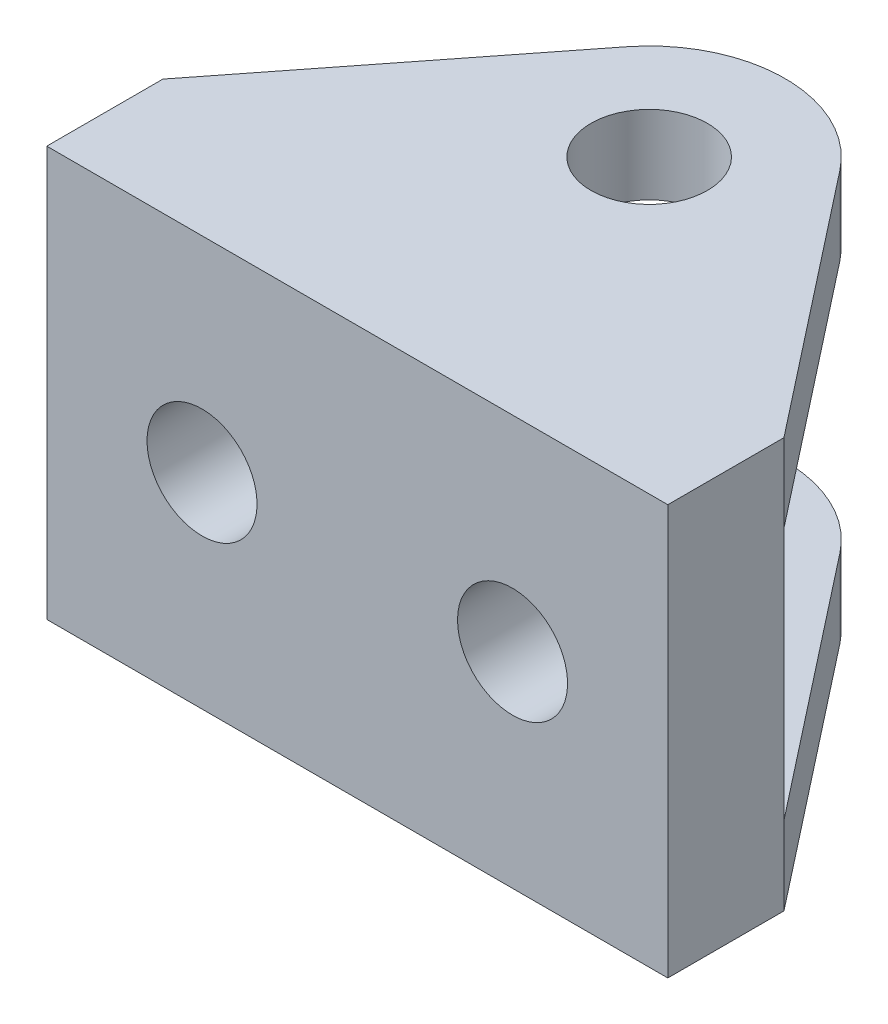
SolidWorks part; units mm, degrees
ref_plane "Front Plane" through (0, 0, 0) normal (0, 0, 1) x (1, 0, 0)
ref_plane "Top Plane" through (0, 0, 0) normal (0, 1, 0) x (1, 0, 0)
ref_plane "Right Plane" through (0, 0, 0) normal (1, 0, 0) x (0, 0, -1)
sketch "Sketch1" plane through (0, 0, 0) normal (0, 1, 0) x (1, 0, 0)
  line L0 (0, 0) -> (50.8, 0)
  line L1 (50.8, 0) -> (50.8, 9.4996)
  line L2 (0, 0) -> (0, 9.4996)
  line L3 (50.8, 9.4996) -> (34.1436, 30.7344)
  line L4 (0, 9.4996) -> (16.6564, 30.7344)
  line L5 (25.4, 0) -> (25.4, 43.8119) construction
  circle A0 centre (25.4, 23.876) radius 4.7625
  arc A1 (34.1436, 30.7344) -> (16.6564, 30.7344) centre (25.4, 23.876) ccw
  dimension "D4" = 6.35
  dimension "D5" = 9.525
  dimension "D1" = 23.876
  dimension "D2" = 50.8
  dimension "D3" = 9.4996
extrude "Boss-Extrude1" add sketch "Sketch1" along normal blind 33.528
sketch "Sketch2" plane through (50.8, 0, 0) normal (1, 0, 0) x (0, 0, -1)
  line L0 (9.4996, 16.764) -> (9.4996, 27.1145)
  line L1 (9.4996, 33.528) -> (9.4996, 0) construction
  line L2 (9.4996, 27.1145) -> (34.9885, 27.1145)
  line L3 (9.4996, 16.764) -> (9.4996, 6.4135)
  line L4 (9.4996, 6.4135) -> (34.9885, 6.4135)
  line L5 (34.9885, 6.4135) -> (34.9885, 27.1145)
  line L6 (34.9885, 0) -> (34.9885, 33.528) construction
  dimension "D1" = 20.701
extrude "Cut-Extrude1" cut sketch "Sketch2" against normal through all
sketch "Sketch3" plane through (0, 0, -9.4996) normal (0, 0, -1) x (-1, 0, 0)
  line L0 (-50.8, 16.764) -> (0, 16.764) construction
  line L1 (-50.8, 27.1145) -> (-50.8, 6.4135) construction
  line L2 (0, 27.1145) -> (0, 6.4135) construction
  line L3 (-25.4, 16.764) -> (-25.4, 27.1145) construction
  line L4 (0, 27.1145) -> (-50.8, 27.1145) construction
  circle A0 centre (-38.1, 16.764) radius 4.5
  circle A1 centre (-12.7, 16.764) radius 4.5
  dimension "D3" = 9
  dimension "D4" = 9
  dimension "D1" = 12.7
  dimension "D2" = 12.7
extrude "Cut-Extrude2" cut sketch "Sketch3" against normal up to surface (9.4996 mm away) up to face at (25.4, 16.764, 0)
ref_axis "Axis1" through (25.4, 82.5272, -23.876) along (0, -1, 0)
ref_plane "Plane1" through (0, 16.764, 0) normal (0, -1, 0) x (-1, 0, 0)
ref_point "Point2"
equation "\"1inch\"=62.1211"
